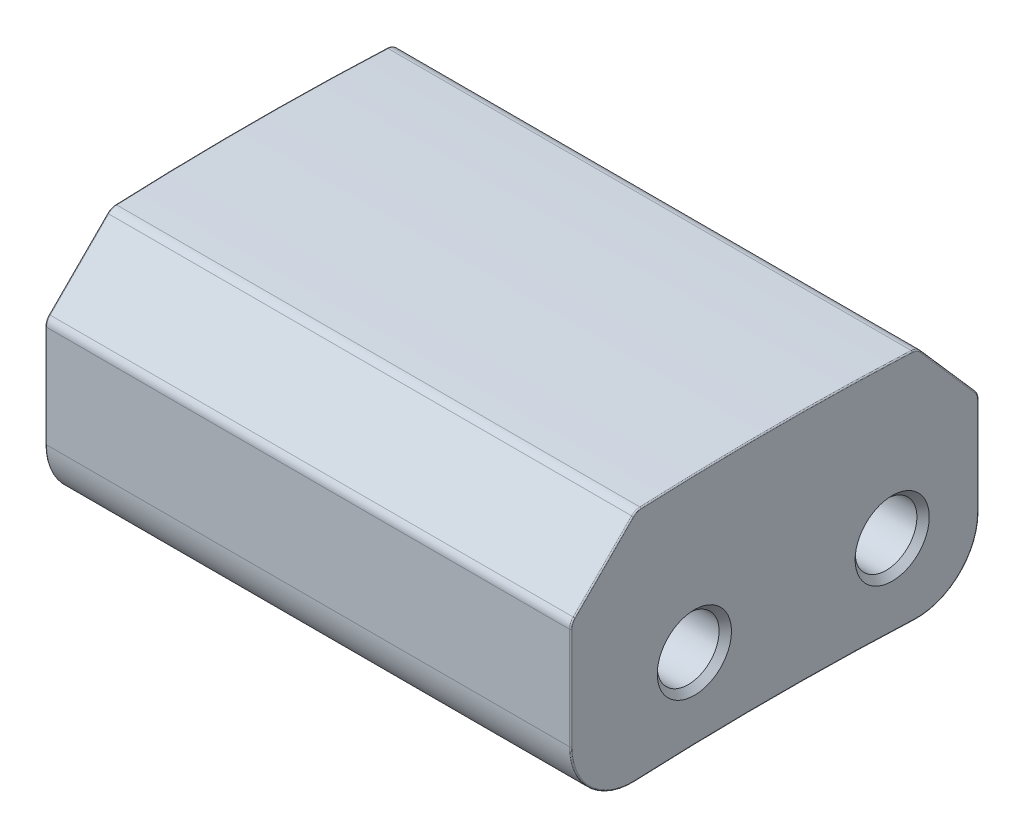
SolidWorks part; units mm, degrees
ref_plane "Front Plane" through (0, 0, 0) normal (0, 0, 1) x (1, 0, 0)
ref_plane "Top Plane" through (0, 0, 0) normal (0, 1, 0) x (1, 0, 0)
ref_plane "Right Plane" through (0, 0, 0) normal (1, 0, 0) x (0, 0, -1)
sketch "Sketch1" plane through (0, 0, 0) normal (0, 1, 0) x (1, 0, 0)
  line L0 (0, -55) -> (0, 55) construction
  line L1 (-4.25, 3.3) -> (4.25, 3.3)
  line L2 (-4.25, 3.3) -> (-4.25, -3.3)
  line L3 (-4.25, -3.3) -> (4.25, -3.3)
  line L4 (4.25, 3.3) -> (4.25, -3.3)
  line L5 (-55, 0) -> (55, 0) construction
  dimension "D1" = 8.5
  dimension "D2" = 4.25
  dimension "D3" = 6.6
  dimension "D4" = 3.3
extrude "Boss-Extrude1" add sketch "Sketch1" along normal blind 4.2
sketch "Sketch2" plane through (4.25, 0, 0) normal (1, 0, 0) x (0, 0, -1)
  line L0 (55, 0) -> (-55, 0) construction
  line L1 (-3.3, 4.2) -> (-3.3, 0) construction
  line L2 (3.3, 4.2) -> (3.3, 0) construction
  line L3 (-3.3, 4.2) -> (3.3, 4.2) construction
  line L4 (-3.3, 3.9) -> (-5.2535, 5.2417)
  line L5 (-5.2535, 5.2417) -> (3.8892, 7.1412)
  line L6 (3.8892, 7.1412) -> (5.6792, 5.0772)
  line L7 (5.6792, 5.0772) -> (3.3, 3.9)
  line L8 (4.7174, 0) -> (0, -2.9048)
  line L9 (0, -2.9048) -> (-4.7004, 0)
  arc A0 (-4.7004, 0) -> (4.7174, 0) centre (0.0085, -49.7778) cw
  arc A1 (-3.3, 3.9) -> (3.3, 3.9) centre (0, -45.991) cw
  dimension "D3" = 50
  dimension "D4" = 50
  dimension "D1" = 0.3
  dimension "D2" = 0.3
extrude "Cut-Extrude1" cut sketch "Sketch2" against normal blind 14.2
chamfer "Chamfer1" distance 1 angle 45 2 edges at (0, 3.9, -3.3) (0, 3.9, 3.3) first distance on face at (0, 3.9545, 0) first distance on face at (0, 2.0063, 3.3)
fillet "Fillet1" radius 1 2 edges at (0, 0.1126, 3.3) (0, 0.1138, -3.3)
fillet "Fillet2" radius 0.2 4 edges at (0, 2.8268, -3.3) (0, 3.9556, -2.3113) (0, 3.9588, 2.2412) (0, 2.9, 3.3)
fillet "Fillet3" radius 0.02 24 edges at (-4.25, 3.9399, -2.3037) (-4.25, 4.009, -0.0313) (-4.25, 3.9455, 2.2353) (-4.25, 3.4312, 2.7688) (-4.25, 2.8937, 3.2848) (-4.25, 1.9936, 3.3) (-4.25, 0.447, 2.9909) (-4.25, 0.2222, -0.0002) (-4.25, 0.4479, -2.991) (-4.25, 1.9612, -3.3) (-4.25, 2.822, -3.2872) (-4.25, 3.3874, -2.809) (4.25, 0.4479, -2.991) (4.25, 0.2222, -0.0002) (4.25, 0.447, 2.9909) (4.25, 1.9936, 3.3) (4.25, 2.8937, 3.2848) (4.25, 3.4312, 2.7688) (4.25, 3.9455, 2.2353) (4.25, 4.009, -0.0313) (4.25, 3.9399, -2.3037) (4.25, 3.3874, -2.809) (4.25, 2.822, -3.2872) (4.25, 1.9612, -3.3)
sketch "Sketch3" plane through (-4.25, 0, 0) normal (-1, 0, 0) x (0, 0, 1)
  line L0 (3.63, 0) -> (-3.63, 0) construction
  line L1 (0, -2.1115) -> (0, 2.1115) construction
  circle A0 centre (-1.9, 1.5) radius 0.5
  circle A1 centre (1.3, 1.5) radius 0.5
  dimension "D1" = 1
  dimension "D2" = 1
  dimension "D3" = 1.5
  dimension "D4" = 1.5
  dimension "D5" = 1.9
  dimension "D6" = 1.3
extrude "Cut-Extrude2" cut sketch "Sketch3" against normal blind 14.2
chamfer "Chamfer2" distance 0.1 angle 45 4 edges at (4.25, 1.5, -1.4) (4.25, 1.5, 1.8) (-4.25, 1.5, -1.4) (-4.25, 1.5, 1.8)
